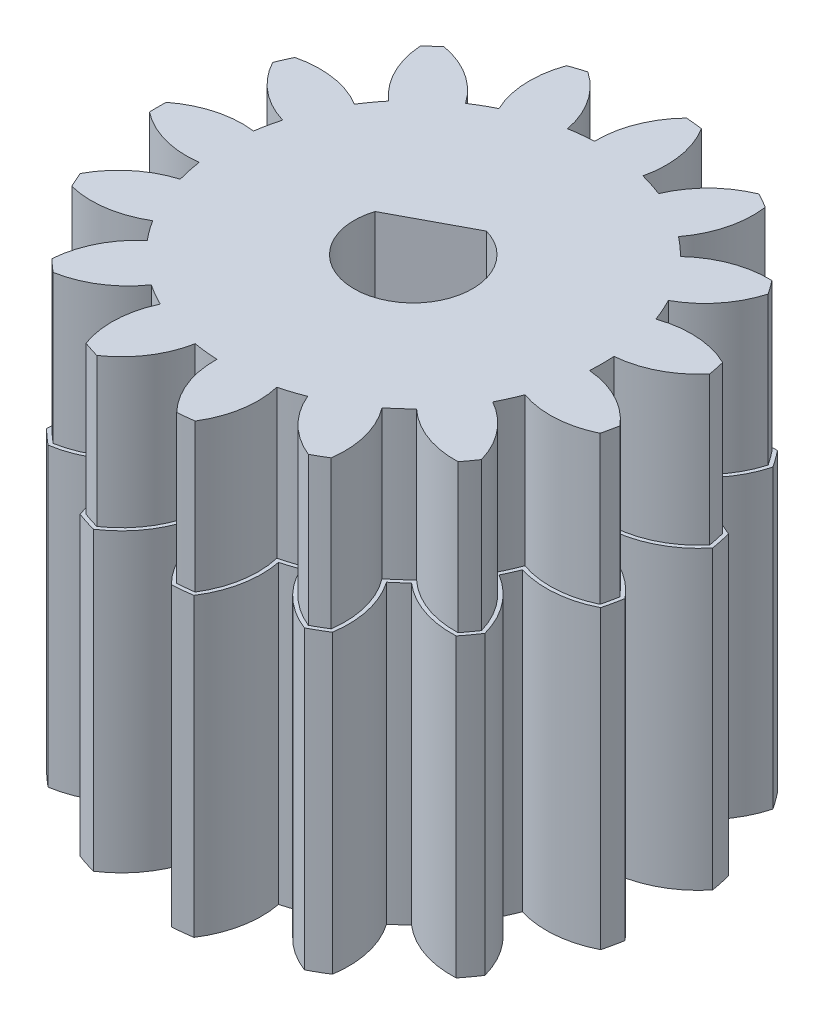
SolidWorks part; units mm, degrees
material "Acrylic (Medium-high impact)"
ref_plane "Front Plane" through (0, 0, 0) normal (0, 0, 1) x (1, 0, 0)
ref_plane "Top Plane" through (0, 0, 0) normal (0, 1, 0) x (1, 0, 0)
ref_plane "Right Plane" through (0, 0, 0) normal (1, 0, 0) x (0, 0, -1)
sketch "Sketch1" plane through (0, 0, 0) normal (0, 1, 0) x (1, 0, 0)
  circle A0 centre (0, 0) radius 56.5317
extrude "Boss-Extrude1" add sketch "Sketch1" along normal blind 5
extrude "Cut-Extrude1" cut sketch "Sketch2" against normal through all contours A74 A73 A72 A71 A70 A18 A19 A20 A21 A13 A12 A11 A10 A25 A24 A23 A22 A29 A28 A27 A26 A33 A32 A31 A30 A37 A36 A35 A34 A41 A40 A39 A38 A45 A44 A43 A42 A49 A48 A47 A46 A53 A52 A51 A50 A57 A56 A55 A54 A61 region at (0, 9.6961, -90.7198)
sketch "Sketch2" plane through (0.054, 9.6961, -2.6905) normal (0, 1, 0) x (0, 0, 1)
  arc A10 (7.0507, 4.4166) -> (7.988, 6.755) centre (4.8627, 6.6506) ccw
  arc A11 (7.988, 6.755) -> (7.5291, 7.0884) centre (2.6905, -0.054) ccw
  arc A12 (7.5291, 7.0884) -> (5.6556, 5.5906) centre (8.3956, 4.0838) ccw
  arc A13 (5.6556, 5.5906) -> (4.7789, 5.9703) centre (2.6905, -0.054) ccw
  arc A18 (3.1034, 6.3087) -> (2.1481, 6.2989) centre (2.6905, -0.054) ccw
  arc A19 (4.2057, 8.4389) -> (3.1034, 6.3087) centre (6.2194, 6.0466) ccw
  arc A20 (4.7605, 8.321) -> (4.2057, 8.4389) centre (2.6905, -0.054) ccw
  arc A21 (4.8554, 5.8036) -> (4.7605, 8.321) centre (1.9479, 6.9545) ccw
  arc A22 (8.4921, 2.2566) -> (10.2994, 4.0116) centre (7.4019, 5.1874) ccw
  arc A23 (10.2994, 4.0116) -> (10.0158, 4.5028) centre (2.6905, -0.054) ccw
  arc A24 (10.0158, 4.5028) -> (7.6951, 3.8966) centre (9.5854, 1.4056) ccw
  arc A25 (7.6951, 3.8966) -> (7.0486, 4.6) centre (2.6905, -0.054) ccw
  arc A26 (8.9303, -0.3029) -> (11.2952, 0.5653) centre (9.1264, 2.818) ccw
  arc A27 (11.2952, 0.5653) -> (11.2359, 1.1294) centre (2.6905, -0.054) ccw
  arc A28 (11.2359, 1.1294) -> (8.8693, 1.5195) centre (9.5829, -1.525) ccw
  arc A29 (8.8693, 1.5195) -> (8.5648, 2.425) centre (2.6905, -0.054) ccw
  arc A30 (8.2896, -2.8193) -> (10.8031, -2.9881) centre (9.7381, -0.0481) ccw
  arc A31 (10.8031, -2.9881) -> (10.9784, -2.4487) centre (2.6905, -0.054) ccw
  arc A32 (10.9784, -2.4487) -> (8.975, -1.1297) centre (8.3887, -4.2012) ccw
  arc A33 (8.975, -1.1297) -> (9.0652, -0.1786) centre (2.6905, -0.054) ccw
  arc A34 (6.6807, -4.8576) -> (8.9083, -6.0342) centre (9.1312, -2.9151) ccw
  arc A35 (8.9083, -6.0342) -> (9.2879, -5.6127) centre (2.6905, -0.054) ccw
  arc A36 (9.2879, -5.6127) -> (7.9942, -3.5929) centre (6.2092, -6.1604) ccw
  arc A37 (7.9942, -3.5929) -> (8.4634, -2.7607) centre (2.6905, -0.054) ccw
  arc A38 (4.3819, -6.0653) -> (5.9384, -8.0462) centre (7.4106, -5.2875) ccw
  arc A39 (5.9384, -8.0462) -> (6.4566, -7.8155) centre (2.6905, -0.054) ccw
  arc A40 (6.4566, -7.8155) -> (6.0962, -5.4441) centre (3.4213, -7.0637) ccw
  arc A41 (6.0962, -5.4441) -> (6.8634, -4.8747) centre (2.6905, -0.054) ccw
  arc A42 (1.7907, -6.2336) -> (2.4068, -8.6763) centre (4.8739, -6.7549) ccw
  arc A43 (2.4068, -8.6763) -> (2.9741, -8.6763) centre (2.6905, -0.054) ccw
  arc A44 (2.9741, -8.6763) -> (3.6094, -6.3634) centre (0.507, -6.7549) ccw
  arc A45 (3.6094, -6.3634) -> (4.5418, -6.1552) centre (2.6905, -0.054) ccw
  arc A46 (-0.645, -5.3334) -> (-1.0757, -7.8155) centre (1.9596, -7.0637) ccw
  arc A47 (-1.0757, -7.8155) -> (-0.5575, -8.0462) centre (2.6905, -0.054) ccw
  arc A48 (-0.5575, -8.0462) -> (0.9637, -6.1917) centre (-2.0297, -5.2875) ccw
  arc A49 (0.9637, -6.1917) -> (1.9001, -6.3808) centre (2.6905, -0.054) ccw
  arc A50 (-2.504, -3.5203) -> (-3.907, -5.6127) centre (-0.8283, -6.1604) ccw
  arc A51 (-3.907, -5.6127) -> (-3.5274, -6.0342) centre (2.6905, -0.054) ccw
  arc A52 (-3.5274, -6.0342) -> (-1.3835, -4.9587) centre (-3.7503, -2.9151) ccw
  arc A53 (-1.3835, -4.9587) -> (-0.6049, -5.5123) centre (2.6905, -0.054) ccw
  arc A54 (-3.4648, -1.1078) -> (-5.5975, -2.4487) centre (-3.0078, -4.2012) ccw
  arc A55 (-5.5975, -2.4487) -> (-5.4222, -2.9881) centre (2.6905, -0.054) ccw
  arc A56 (-5.4222, -2.9881) -> (-3.0262, -2.8776) centre (-4.3572, -0.0481) ccw
  arc A57 (-3.0262, -2.8776) -> (-2.5401, -3.7001) centre (2.6905, -0.054) ccw
  arc A58 (-3.3613, 1.4869) -> (-5.855, 1.1294) centre (-4.202, -1.525) ccw
  arc A59 (-5.855, 1.1294) -> (-5.9143, 0.5653) centre (2.6905, -0.054) ccw
  arc A60 (-5.9143, 0.5653) -> (-3.6805, -0.3083) centre (-3.7455, 2.818) ccw
  arc A61 (-3.6805, -0.3083) -> (-3.5709, -1.2574) centre (2.6905, -0.054) ccw
  arc A62 (-2.2114, 3.8151) -> (-4.6349, 4.5028) centre (-4.2045, 1.4056) ccw
  arc A63 (-4.6349, 4.5028) -> (-4.9185, 4.0116) centre (2.6905, -0.054) ccw
  arc A64 (-4.9185, 4.0116) -> (-3.2331, 2.3049) centre (-2.021, 5.1874) ccw
  arc A65 (-3.2331, 2.3049) -> (-3.5191, 1.3934) centre (2.6905, -0.054) ccw
  arc A66 (-0.2139, 5.4744) -> (-2.1482, 7.0884) centre (-3.0147, 4.0838) ccw
  arc A67 (-2.1482, 7.0884) -> (-2.6071, 6.755) centre (2.6905, -0.054) ccw
  arc A68 (-2.6071, 6.755) -> (-1.7616, 4.5103) centre (0.5182, 6.6506) ccw
  arc A69 (-1.7616, 4.5103) -> (-2.3936, 3.7939) centre (2.6905, -0.054) ccw
  arc A70 (2.2858, 6.1777) -> (1.1752, 8.4389) centre (-0.8385, 6.0466) ccw
  arc A71 (1.1752, 8.4389) -> (0.6204, 8.321) centre (2.6905, -0.054) ccw
  arc A72 (0.6204, 8.321) -> (0.4798, 5.9265) centre (3.433, 6.9545) ccw
  arc A73 (0.4798, 5.9265) -> (-0.389, 5.5291) centre (2.6905, -0.054) ccw
  circle A74 centre (2.6905, -0.054) radius 93.3605
  point P109 (2.6905, -0.054)
sketch "Sketch3" plane through (0, 5, 0) normal (0, 1, 0) x (1, 0, 0)
  line L0 (-1.9022, 0.6178) -> (0.5473, 1.9236)
  arc A0 (-1.9022, 0.6178) -> (0.5473, 1.9236) centre (0, 0) ccw
  dimension "D1" = 4
  dimension "D2" = 1.44
  dimension "D3" = 6.7201
  dimension "D5" = 16.9973
extrude "Cut-Extrude2" cut sketch "Sketch3" against normal through all
sketch "Sketch4" plane through (0, 0, 0) normal (0, -1, 0) x (1, 0, 0)
  line L2 (0.5944, -1.8354) -> (-1.8552, -0.5295)
  line L3 (0.5944, -1.8354) -> (-1.8552, -0.5295)
  arc A62 (0.52, -1.8275) -> (-1.8071, -0.5869) centre (0, 0) ccw
  arc A63 (0.52, -1.8275) -> (-1.8071, -0.5869) centre (0, 0) ccw
  arc A120 (5.8129, -2.9154) -> (6.0561, -2.369) centre (0, 0) ccw
  arc A121 (6.0561, -2.369) -> (8.4839, -2.1577) centre (7.0085, 0.7425) ccw
  arc A122 (8.4839, -2.1577) -> (8.6281, -1.4795) centre (0, 0) ccw
  arc A123 (8.6281, -1.4795) -> (6.4961, -0.2991) centre (6.1005, -3.5289) ccw
  arc A124 (6.4961, -0.2991) -> (6.4961, 0.2991) centre (0, 0) ccw
  arc A125 (6.4961, 0.2991) -> (8.6281, 1.4795) centre (6.1005, 3.5289) ccw
  arc A126 (8.6281, 1.4795) -> (8.4839, 2.1577) centre (0, 0) ccw
  arc A127 (8.4839, 2.1577) -> (6.0561, 2.369) centre (7.0085, -0.7425) ccw
  arc A128 (6.0561, 2.369) -> (5.8129, 2.9154) centre (0, 0) ccw
  arc A129 (5.8129, 2.9154) -> (7.2804, 4.861) centre (4.1378, 5.7052) ccw
  arc A130 (7.2804, 4.861) -> (6.8728, 5.4219) centre (0, 0) ccw
  arc A131 (6.8728, 5.4219) -> (4.569, 4.6274) centre (6.7046, 2.1723) ccw
  arc A132 (4.569, 4.6274) -> (4.1245, 5.0277) centre (0, 0) ccw
  arc A133 (4.1245, 5.0277) -> (4.6738, 7.4019) centre (1.4595, 6.8949) ccw
  arc A134 (4.6738, 7.4019) -> (4.0733, 7.7486) centre (0, 0) ccw
  arc A135 (4.0733, 7.7486) -> (2.2918, 6.0858) centre (5.2414, 4.7115) ccw
  arc A136 (2.2918, 6.0858) -> (1.723, 6.2706) centre (0, 0) ccw
  arc A137 (1.723, 6.2706) -> (1.2591, 8.663) centre (-1.471, 6.8925) ccw
  arc A138 (1.2591, 8.663) -> (0.5695, 8.7355) centre (0, 0) ccw
  arc A139 (0.5695, 8.7355) -> (-0.3816, 6.4918) centre (2.8719, 6.436) ccw
  arc A140 (-0.3816, 6.4918) -> (-0.9765, 6.4293) centre (0, 0) ccw
  arc A141 (-0.9765, 6.4293) -> (-2.3733, 8.4262) centre (-4.1473, 5.6982) ccw
  arc A142 (-2.3733, 8.4262) -> (-3.0327, 8.2119) centre (0, 0) ccw
  arc A143 (-3.0327, 8.2119) -> (-2.9891, 5.7753) centre (0.0059, 7.0477) ccw
  arc A144 (-2.9891, 5.7753) -> (-3.5071, 5.4763) centre (0, 0) ccw
  arc A145 (-3.5071, 5.4763) -> (-5.5953, 6.7324) centre (-6.1064, 3.5188) ccw
  arc A146 (-5.5953, 6.7324) -> (-6.1106, 6.2684) centre (0, 0) ccw
  arc A147 (-6.1106, 6.2684) -> (-5.0797, 4.0603) centre (-2.8612, 6.4408) ccw
  arc A148 (-5.0797, 4.0603) -> (-5.4313, 3.5764) centre (0, 0) ccw
  arc A149 (-5.4313, 3.5764) -> (-7.8499, 3.8745) centre (-7.0097, 0.7308) ccw
  arc A150 (-7.8499, 3.8745) -> (-8.1319, 3.2411) centre (0, 0) ccw
  arc A151 (-8.1319, 3.2411) -> (-6.292, 1.6432) centre (-5.2335, 4.7202) ccw
  arc A152 (-6.292, 1.6432) -> (-6.4163, 1.0581) centre (0, 0) ccw
  arc A153 (-6.4163, 1.0581) -> (-8.7471, 0.3467) centre (-6.7009, -2.1834) ccw
  arc A154 (-8.7471, 0.3467) -> (-8.7471, -0.3467) centre (0, 0) ccw
  arc A155 (-8.7471, -0.3467) -> (-6.4163, -1.0581) centre (-6.7009, 2.1834) ccw
  arc A156 (-6.4163, -1.0581) -> (-6.292, -1.6432) centre (0, 0) ccw
  arc A157 (-6.292, -1.6432) -> (-8.1319, -3.2411) centre (-5.2335, -4.7202) ccw
  arc A158 (-8.1319, -3.2411) -> (-7.8499, -3.8745) centre (0, 0) ccw
  arc A159 (-7.8499, -3.8745) -> (-5.4313, -3.5764) centre (-7.0097, -0.7308) ccw
  arc A160 (-5.4313, -3.5764) -> (-5.0797, -4.0603) centre (0, 0) ccw
  arc A161 (-5.0797, -4.0603) -> (-6.1106, -6.2684) centre (-2.8612, -6.4408) ccw
  arc A162 (-6.1106, -6.2684) -> (-5.5953, -6.7324) centre (0, 0) ccw
  arc A163 (-5.5953, -6.7324) -> (-3.5071, -5.4763) centre (-6.1064, -3.5188) ccw
  arc A164 (-3.5071, -5.4763) -> (-2.9891, -5.7753) centre (0, 0) ccw
  arc A165 (-2.9891, -5.7753) -> (-3.0327, -8.2119) centre (0.0059, -7.0477) ccw
  arc A166 (-3.0327, -8.2119) -> (-2.3733, -8.4262) centre (0, 0) ccw
  arc A167 (-2.3733, -8.4262) -> (-0.9765, -6.4293) centre (-4.1473, -5.6982) ccw
  arc A168 (-0.9765, -6.4293) -> (-0.3816, -6.4918) centre (0, 0) ccw
  arc A169 (-0.3816, -6.4918) -> (0.5695, -8.7355) centre (2.8719, -6.436) ccw
  arc A170 (0.5695, -8.7355) -> (1.2591, -8.663) centre (0, 0) ccw
  arc A171 (1.2591, -8.663) -> (1.723, -6.2706) centre (-1.471, -6.8925) ccw
  arc A172 (1.723, -6.2706) -> (2.2918, -6.0858) centre (0, 0) ccw
  arc A173 (2.2918, -6.0858) -> (4.0733, -7.7486) centre (5.2414, -4.7115) ccw
  arc A174 (4.0733, -7.7486) -> (4.6738, -7.4019) centre (0, 0) ccw
  arc A175 (4.6738, -7.4019) -> (4.1245, -5.0277) centre (1.4595, -6.8949) ccw
  arc A176 (4.1245, -5.0277) -> (4.569, -4.6274) centre (0, 0) ccw
  arc A177 (4.569, -4.6274) -> (6.8728, -5.4219) centre (6.7046, -2.1723) ccw
  arc A178 (6.8728, -5.4219) -> (7.2804, -4.861) centre (0, 0) ccw
  arc A179 (7.2804, -4.861) -> (5.8129, -2.9154) centre (4.1378, -5.7052) ccw
  arc A180 (5.8129, -2.9154) -> (6.0561, -2.369) centre (0, 0) ccw
  arc A181 (6.0561, -2.369) -> (8.4839, -2.1577) centre (7.0085, 0.7425) ccw
  arc A182 (8.4839, -2.1577) -> (8.6281, -1.4795) centre (0, 0) ccw
  arc A183 (8.6281, -1.4795) -> (6.4961, -0.2991) centre (6.1005, -3.5289) ccw
  arc A184 (6.4961, -0.2991) -> (6.4961, 0.2991) centre (0, 0) ccw
  arc A185 (6.4961, 0.2991) -> (8.6281, 1.4795) centre (6.1005, 3.5289) ccw
  arc A186 (8.6281, 1.4795) -> (8.4839, 2.1577) centre (0, 0) ccw
  arc A187 (8.4839, 2.1577) -> (6.0561, 2.369) centre (7.0085, -0.7425) ccw
  arc A188 (6.0561, 2.369) -> (5.8129, 2.9154) centre (0, 0) ccw
  arc A189 (5.8129, 2.9154) -> (7.2804, 4.861) centre (4.1378, 5.7052) ccw
  arc A190 (7.2804, 4.861) -> (6.8728, 5.4219) centre (0, 0) ccw
  arc A191 (6.8728, 5.4219) -> (4.569, 4.6274) centre (6.7046, 2.1723) ccw
  arc A192 (4.569, 4.6274) -> (4.1245, 5.0277) centre (0, 0) ccw
  arc A193 (4.1245, 5.0277) -> (4.6738, 7.4019) centre (1.4595, 6.8949) ccw
  arc A194 (4.6738, 7.4019) -> (4.0733, 7.7486) centre (0, 0) ccw
  arc A195 (4.0733, 7.7486) -> (2.2918, 6.0858) centre (5.2414, 4.7115) ccw
  arc A196 (2.2918, 6.0858) -> (1.723, 6.2706) centre (0, 0) ccw
  arc A197 (1.723, 6.2706) -> (1.2591, 8.663) centre (-1.471, 6.8925) ccw
  arc A198 (1.2591, 8.663) -> (0.5695, 8.7355) centre (0, 0) ccw
  arc A199 (0.5695, 8.7355) -> (-0.3816, 6.4918) centre (2.8719, 6.436) ccw
  arc A200 (-0.3816, 6.4918) -> (-0.9765, 6.4293) centre (0, 0) ccw
  arc A201 (-0.9765, 6.4293) -> (-2.3733, 8.4262) centre (-4.1473, 5.6982) ccw
  arc A202 (-2.3733, 8.4262) -> (-3.0327, 8.2119) centre (0, 0) ccw
  arc A203 (-3.0327, 8.2119) -> (-2.9891, 5.7753) centre (0.0059, 7.0477) ccw
  arc A204 (-2.9891, 5.7753) -> (-3.5071, 5.4763) centre (0, 0) ccw
  arc A205 (-3.5071, 5.4763) -> (-5.5953, 6.7324) centre (-6.1064, 3.5188) ccw
  arc A206 (-5.5953, 6.7324) -> (-6.1106, 6.2684) centre (0, 0) ccw
  arc A207 (-6.1106, 6.2684) -> (-5.0797, 4.0603) centre (-2.8612, 6.4408) ccw
  arc A208 (-5.0797, 4.0603) -> (-5.4313, 3.5764) centre (0, 0) ccw
  arc A209 (-5.4313, 3.5764) -> (-7.8499, 3.8745) centre (-7.0097, 0.7308) ccw
  arc A210 (-7.8499, 3.8745) -> (-8.1319, 3.2411) centre (0, 0) ccw
  arc A211 (-8.1319, 3.2411) -> (-6.292, 1.6432) centre (-5.2335, 4.7202) ccw
  arc A212 (-6.292, 1.6432) -> (-6.4163, 1.0581) centre (0, 0) ccw
  arc A213 (-6.4163, 1.0581) -> (-8.7471, 0.3467) centre (-6.7009, -2.1834) ccw
  arc A214 (-8.7471, 0.3467) -> (-8.7471, -0.3467) centre (0, 0) ccw
  arc A215 (-8.7471, -0.3467) -> (-6.4163, -1.0581) centre (-6.7009, 2.1834) ccw
  arc A216 (-6.4163, -1.0581) -> (-6.292, -1.6432) centre (0, 0) ccw
  arc A217 (-6.292, -1.6432) -> (-8.1319, -3.2411) centre (-5.2335, -4.7202) ccw
  arc A218 (-8.1319, -3.2411) -> (-7.8499, -3.8745) centre (0, 0) ccw
  arc A219 (-7.8499, -3.8745) -> (-5.4313, -3.5764) centre (-7.0097, -0.7308) ccw
  arc A220 (-5.4313, -3.5764) -> (-5.0797, -4.0603) centre (0, 0) ccw
  arc A221 (-5.0797, -4.0603) -> (-6.1106, -6.2684) centre (-2.8612, -6.4408) ccw
  arc A222 (-6.1106, -6.2684) -> (-5.5953, -6.7324) centre (0, 0) ccw
  arc A223 (-5.5953, -6.7324) -> (-3.5071, -5.4763) centre (-6.1064, -3.5188) ccw
  arc A224 (-3.5071, -5.4763) -> (-2.9891, -5.7753) centre (0, 0) ccw
  arc A225 (-2.9891, -5.7753) -> (-3.0327, -8.2119) centre (0.0059, -7.0477) ccw
  arc A226 (-3.0327, -8.2119) -> (-2.3733, -8.4262) centre (0, 0) ccw
  arc A227 (-2.3733, -8.4262) -> (-0.9765, -6.4293) centre (-4.1473, -5.6982) ccw
  arc A228 (-0.9765, -6.4293) -> (-0.3816, -6.4918) centre (0, 0) ccw
  arc A229 (-0.3816, -6.4918) -> (0.5695, -8.7355) centre (2.8719, -6.436) ccw
  arc A230 (0.5695, -8.7355) -> (1.2591, -8.663) centre (0, 0) ccw
  arc A231 (1.2591, -8.663) -> (1.723, -6.2706) centre (-1.471, -6.8925) ccw
  arc A232 (1.723, -6.2706) -> (2.2918, -6.0858) centre (0, 0) ccw
  arc A233 (2.2918, -6.0858) -> (4.0733, -7.7486) centre (5.2414, -4.7115) ccw
  arc A234 (4.0733, -7.7486) -> (4.6738, -7.4019) centre (0, 0) ccw
  arc A235 (4.6738, -7.4019) -> (4.1245, -5.0277) centre (1.4595, -6.8949) ccw
  arc A236 (4.1245, -5.0277) -> (4.569, -4.6274) centre (0, 0) ccw
  arc A237 (4.569, -4.6274) -> (6.8728, -5.4219) centre (6.7046, -2.1723) ccw
  arc A238 (6.8728, -5.4219) -> (7.2804, -4.861) centre (0, 0) ccw
  arc A239 (7.2804, -4.861) -> (5.8129, -2.9154) centre (4.1378, -5.7052) ccw
  dimension "D1" = 0.127
  dimension "D2" = 0.1
  dimension "D3" = 0.1
extrude "Boss-Extrude2" add sketch "Sketch4" along normal blind 10 contours A238 A239 A180 A181 A182 A183 A184 A185 A186 A187 A188 A189 A190 A191 A192 A193 A194 A195 A196 A197 A198 A199 A200 A201 A202 A203 A204 A205 A206 A207 A208 A209 A210 A211 A212 A213 A214 A215 A216 A217 A218 A219 A220 A221 A222 A223 A224 A225 A226 A227 A228 region at (6.5389, 0, -3.894)
